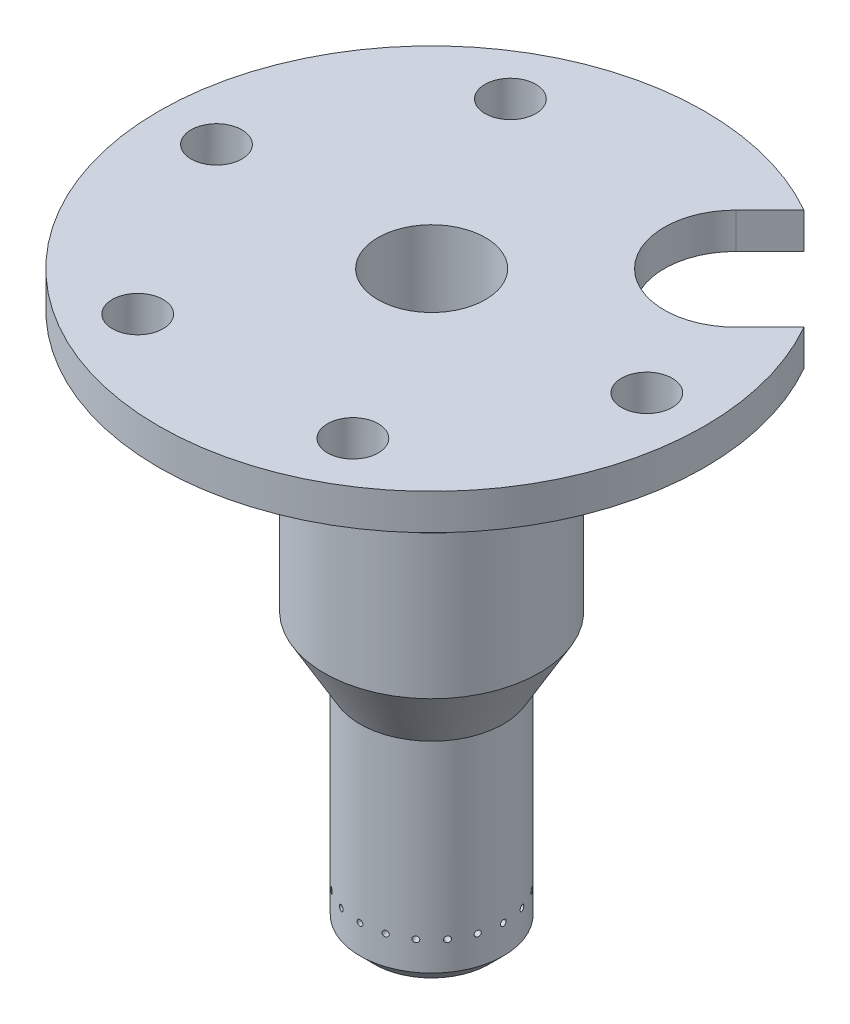
SolidWorks part; units mm, degrees
ref_plane "Front Plane" through (0, 0, 0) normal (0, 0, 1) x (1, 0, 0)
ref_plane "Top Plane" through (0, 0, 0) normal (0, 1, 0) x (1, 0, 0)
ref_plane "Right Plane" through (0, 0, 0) normal (1, 0, 0) x (0, 0, -1)
sketch "Sketch1" plane through (0, 0, 0) normal (0, 0, 1) x (1, 0, 0)
  line L0 (0, 0) -> (0, 66.0706) construction
  line L1 (6.35, 0) -> (6.35, 19.05)
  line L2 (6.35, 0) -> (0, 0)
  line L4 (0, 50.8) -> (0, 0)
  line L5 (6.35, 19.05) -> (9.525, 24.5493)
  line L6 (9.525, 24.5493) -> (9.525, 37.2493)
  line L7 (12.7, 50.8) -> (0, 50.8)
  line L11 (9.525, 37.2493) -> (12.7, 40.4243)
  line L12 (12.7, 40.4243) -> (12.7, 47.625)
  line L14 (12.7, 50.8) -> (24.1554, 50.8)
  line L15 (24.1554, 50.8) -> (24.1554, 47.625)
  line L16 (24.1554, 47.625) -> (12.7, 47.625)
  point P14 (0, 0)
  dimension "D1" = 12.7
  dimension "D2" = 25.4
  dimension "D3" = 19.05
  dimension "D4" = 30
  dimension "D5" = 19.05
  dimension "D6" = 50.8
  dimension "D7" = 48.3108
  dimension "D8" = 45
  dimension "D9" = 12.7
  dimension "D10" = 3.175
revolve "Revolve1" add sketch "Sketch1" angle 360 about L0
chamfer "Chamfer1" distance 1.27 angle 45 1 edges at (0, 0, -6.35)
hole_wizard "#76 (0.02) Diameter Hole1" positions "3DSketch1" profile "Sketch3" hole size "#76" standard "ANSI Inch"
sketch3d "3DSketch1"
  point P0 (6.35, 3.81, 0)
  dimension "D1" = 3.81
sketch "Sketch3" plane through (6.35, 3.81, 0) normal (0, 1, 0) x (0, 0, -1)
  line L0 (0, 0) -> (0, 2.6926)
  line L1 (0, 2.6926) -> (0.254, 2.54)
  line L2 (0.254, 2.54) -> (0.254, 0)
  line L5 (0.254, 0) -> (0, 0)
  line L10 (0, 2.6926) -> (-0.254, 2.54) construction
  line L11 (0, -6.35) -> (0, 107.95) construction
  dimension "Hole Dia." = 0.508
  dimension "Hole Depth" = 2.54
  dimension "Drill Angle" = 118
pattern_circular "CirPattern2" count 20 over 360 about axis through (0, 0, 0) along (0, -1, 0) of "#76 (0.02) Diameter Hole1" reverse direction yes
hole_wizard "3/8 (0.375) Diameter Hole2" positions "Sketch6" profile "Sketch7" hole size "3/8" standard "ANSI Inch"
sketch "Sketch6" plane through (0, 50.8, 0) normal (0, 1, 0) x (1, 0, 0)
  point P0 (0, 0)
sketch "Sketch7" plane through (0, 50.8, 0) normal (1, 0, 0) x (0, 0, 1)
  line L0 (0, 0) -> (0, 49.8516)
  line L1 (0, 49.8516) -> (4.7625, 46.99)
  line L2 (4.7625, 46.99) -> (4.7625, 0)
  line L5 (4.7625, 0) -> (0, 0)
  line L10 (0, 49.8516) -> (-4.7625, 46.99) construction
  line L11 (0, -6.35) -> (0, 107.95) construction
  dimension "Hole Dia." = 9.525
  dimension "Hole Depth" = 46.99
  dimension "Drill Angle" = 118
hole_wizard "#8 Clearance Hole1" positions "Sketch8" profile "Sketch9" hole size "#8" standard "ANSI Inch" end condition through all
sketch "Sketch8" plane through (0, 50.8, 0) normal (0, 1, 0) x (1, 0, 0)
  circle A0 centre (0, 0) radius 19.05 construction
  point P0 (19.05, 0)
  dimension "D1" = 38.1
sketch "Sketch9" plane through (19.05, 50.8, 0) normal (1, 0, 0) x (0, 0, 1)
  line L0 (0, 0) -> (0, 50.8)
  line L1 (0, 50.8) -> (2.2479, 50.8)
  line L2 (2.2479, 50.8) -> (2.2479, 0)
  line L5 (2.2479, 0) -> (0, 0)
  line L11 (0, -6.35) -> (0, 107.95) construction
  dimension "Thru Hole Dia." = 4.4958
  dimension "Thru Hole Depth" = 50.8
pattern_circular "CirPattern3" count 6 over 360 about axis through (0, 0, 0) along (0, -1, 0) skipping 1 of "#8 Clearance Hole1" reverse direction yes
ref_plane "Plane1" through (0, 0, 0) normal (-1, 0, 0) x (0, 0, -1)
sketch "Sketch11" plane through (0, 0, 0) normal (-1, 0, 0) x (0, 0, -1)
  line L0 (11.6619, -43.2939) -> (12.7889, -43.1953)
  line L1 (12.7889, -43.1953) -> (12.7889, -45.7547)
  line L2 (12.7889, -45.7547) -> (11.6619, -45.6561)
  line L3 (11.43, -45.4031) -> (11.43, -43.5469)
  line L4 (0, 50) -> (0, -50) construction
  arc A0 (11.6619, -45.6561) -> (11.43, -45.4031) centre (11.684, -45.4031) cw
  arc A1 (11.43, -43.5469) -> (11.6619, -43.2939) centre (11.684, -43.5469) cw
revolve "Groove for AS 568-020, O-Ring1" cut sketch "Sketch11"
sketch "Sketch12" plane through (0, 50.8, 0) normal (0, 1, 0) x (1, 0, 0)
  line L0 (11.9896, 20.9698) -> (8.9803, 17.9605)
  line L1 (17.9605, 8.9803) -> (20.9698, 11.9896)
  line L2 (0, 0) -> (17.0804, 17.0804) construction
  line L3 (0, 0) -> (24.1554, 0) construction
  circle A0 centre (0, 0) radius 24.1554 construction
  arc A1 (8.9803, 17.9605) -> (17.9605, 8.9803) centre (13.4704, 13.4704) ccw
  point P7 (17.4522, 16.7004)
  dimension "D1" = 6.35
  dimension "D2" = 19.05
  dimension "D3" = 45
extrude "Cut-Extrude1" cut sketch "Sketch12" against normal blind 3.175 and the other way through all
